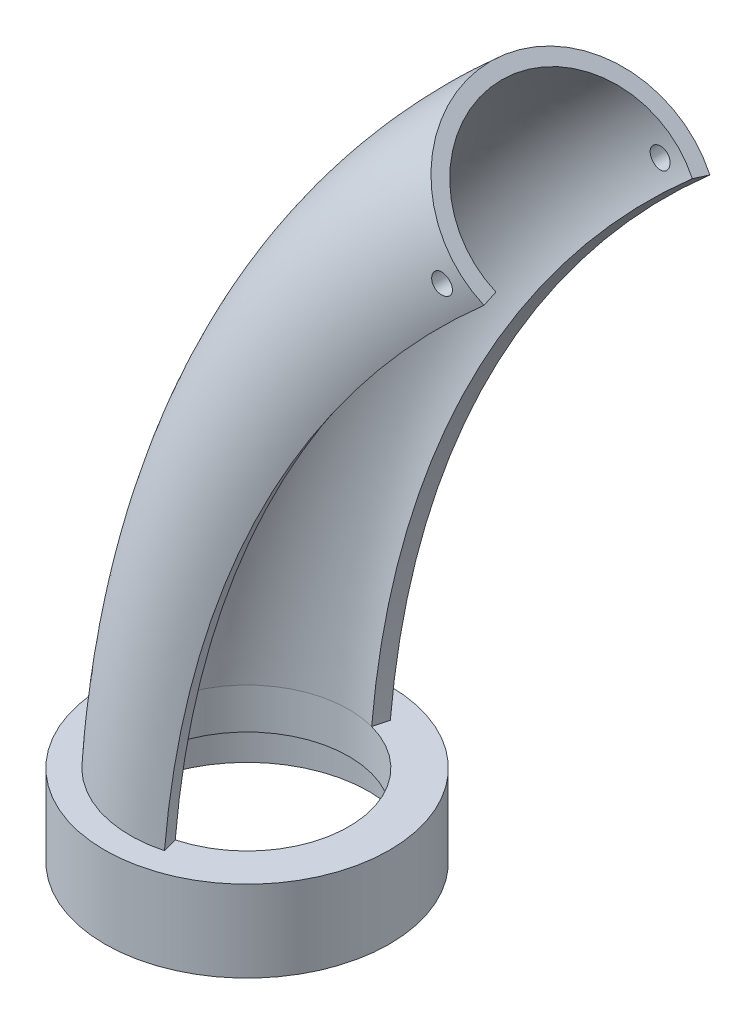
SolidWorks part; units mm, degrees
material "Plain Carbon Steel"
ref_plane "Front Plane" through (0, 0, 0) normal (0, 0, 1) x (1, 0, 0)
ref_plane "Top Plane" through (0, 0, 0) normal (0, 1, 0) x (1, 0, 0)
ref_plane "Right Plane" through (0, 0, 0) normal (1, 0, 0) x (0, 0, -1)
sketch "Sketch2" plane through (0, 0, 0) normal (0, 1, 0) x (1, 0, 0)
  circle A0 centre (0, 0) radius 63.5
  circle A1 centre (0, 0) radius 76.2
  circle A2 centre (0, 0) radius 88.9
  dimension "D1" = 127
  dimension "D2" = 152.4
  dimension "D3" = 177.8
extrude "Boss-Extrude1" add sketch "Sketch2" along normal blind 50.8 contours A1 A0 | A2 A1 region at (-74.0447, 0, 0) region at (-86.3855, 0, 0)
extrude "Cut-Extrude1" cut sketch "Sketch2<4>" along normal blind 25.4 contours A1 A0 region at (-74.0447, 0, 0)
sketch "Sketch2<4>" plane through (0, 0, 0) normal (0, 1, 0) x (1, 0, 0) same geometry as "Sketch2"
sketch "Sketch3" plane through (0, 0, 0) normal (0, 0, 1) x (1, 0, 0)
  line L0 (-88.9, 0) -> (88.9, 0) construction
  line L1 (0, 0) -> (0, -13.8545) construction
  arc A0 (0, 0) -> (206.3875, 457.2) centre (609.6, 0) cw
  dimension "D2" = 609.6
  dimension "D1" = 457.2
sketch "Sketch4" plane through (0, 50.8, 0) normal (0, 1, 0) x (1, 0, 0)
  line L0 (18.9003, 70.5367) -> (0, 0) construction
  line L1 (0, 0) -> (18.9003, -70.5367) construction
  line L2 (16.435, 61.3363) -> (18.9003, 70.5367)
  line L3 (18.9003, -70.5367) -> (16.435, -61.3363)
  line L4 (0, 0) -> (206.3875, 0) construction
  arc A0 (16.435, -61.3363) -> (16.435, 61.3363) centre (0, 0) cw
  arc A1 (18.9003, 70.5367) -> (18.9003, -70.5367) centre (0, 0) ccw
  circle A4 centre (0, 0) radius 63.5 construction
  dimension "D1" = 150
  dimension "D2" = 75
  dimension "D3" = 9.525
sweep "Sweep1" add profiles "Sketch4" path "Sketch3"
sketch "Sketch5" plane through (0, 0, 0) normal (0, 0, 1) x (1, 0, 0)
  circle A0 centre (194.619, 446.5455) radius 6.35
  arc A1 (206.3875, 457.2) -> (0, 0) centre (609.6, 0) ccw construction
  dimension "D1" = 12.7
  dimension "D2" = 15.875
extrude "Cut-Extrude2" cut sketch "Sketch5" against normal through all both and the other way through all
